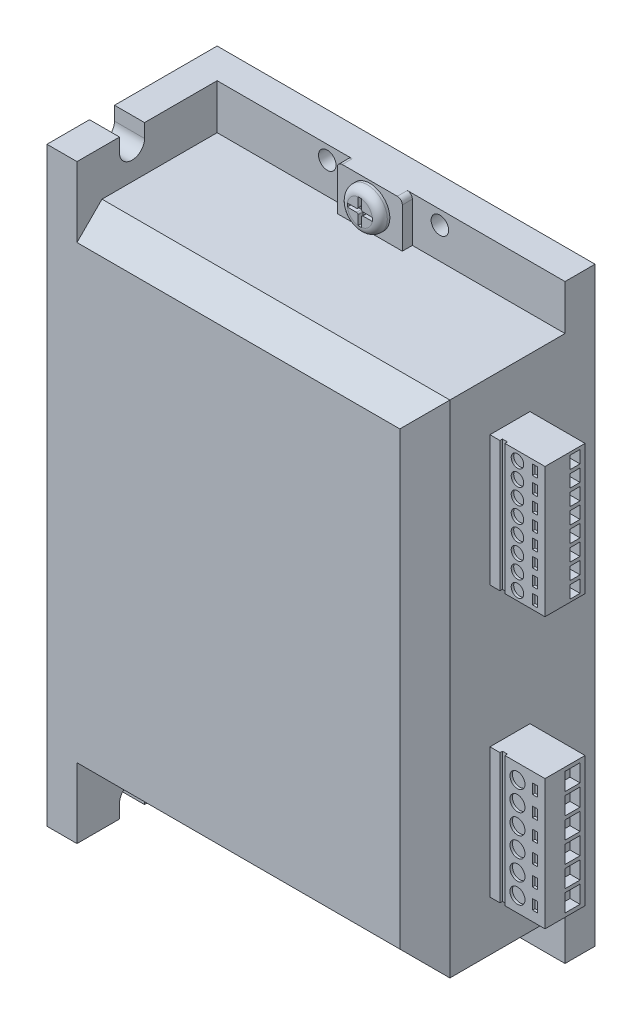
SolidWorks part; units mm, degrees
ref_plane "Front Plane" through (0, 0, 0) normal (0, 0, 1) x (1, 0, 0)
ref_plane "Top Plane" through (0, 0, 0) normal (0, 1, 0) x (1, 0, 0)
ref_plane "Right Plane" through (0, 0, 0) normal (1, 0, 0) x (0, 0, -1)
ref_axis "Axis_X" through (-88.99, 0, 0) along (1, 0, 0)
ref_axis "Axis_Y" through (0, 55, 0) along (0, -1, 0)
ref_axis "Axis_Z" through (0, 0, -88.99) along (0, 0, 1)
sketch "Sketch1" plane through (0, 0, 0) normal (0, 0, 1) x (1, 0, 0)
  line L0 (0, 0) -> (75.5, 0) construction
  line L1 (0, 59) -> (75.5, 59)
  line L2 (0, 59) -> (0, -59)
  line L3 (0, -59) -> (75.5, -59)
  line L4 (75.5, 59) -> (75.5, -59)
  dimension "FIX_101" = 118
  dimension "FIX_102" = 75.5
extrude "Boss-Extrude1" add sketch "Sketch1" along normal blind 34
sketch "Sketch2" plane through (0, 0, 34) normal (0, 0, 1) x (1, 0, 0)
  line L0 (0, 0) -> (75.5, 0) construction
  line L1 (0, 59) -> (0, -59) construction
  line L2 (75.5, -59) -> (75.5, 59) construction
  line L3 (75.5, 59) -> (0, 59) construction
  line L4 (6, 59) -> (75.5, 59)
  line L5 (6, 59) -> (6, 50)
  line L6 (6, 50) -> (75.5, 50)
  line L7 (75.5, 59) -> (75.5, 50)
  line L9 (75.5, -59) -> (6, -59)
  line L10 (75.5, -59) -> (75.5, -50)
  line L11 (75.5, -50) -> (6, -50)
  line L12 (6, -59) -> (6, -50)
  dimension "FIX_104" = 6
  dimension "FIX_105" = 9
extrude "Cut-Extrude1" cut sketch "Sketch2" against normal offset from surface (28 mm away) 6 up to face at (37.75, 0, 0)
sketch "Sketch3" plane through (0, 0, 6) normal (0, 0, 1) x (1, 0, 0)
  line L0 (75.5, 59) -> (6, 59) construction
  line L1 (33, 59) -> (44, 59)
  line L2 (32, 58) -> (32, 50)
  line L3 (32, 50) -> (45, 50)
  line L4 (45, 58) -> (45, 50)
  line L5 (6, 50) -> (75.5, 50) construction
  line L6 (75.5, -50) -> (6, -50) construction
  line L7 (32, -50) -> (45, -50)
  line L8 (32, -50) -> (32, -58)
  line L9 (33, -59) -> (44, -59)
  line L10 (45, -50) -> (45, -58)
  line L11 (6, -59) -> (75.5, -59) construction
  arc A0 (44, -59) -> (45, -58) centre (44, -58) ccw
  arc A1 (33, -59) -> (32, -58) centre (33, -58) cw
  arc A2 (44, 59) -> (45, 58) centre (44, 58) cw
  arc A3 (32, 58) -> (33, 59) centre (33, 58) cw
  point P19 (45, -59)
  point P26 (32, 59)
  dimension "FIX_109" = 1
  dimension "FIX_107" = 13
  dimension "FIX_108" = 32
extrude "Boss-Extrude2" add sketch "Sketch3" along normal blind 2
hole_wizard "DiameterHole1" positions "Sketch4" profile "Sketch5" hole size "Ø3.5" standard "JIS" end condition through all
sketch "Sketch4" plane through (0, 0, 6) normal (0, 0, 1) x (1, 0, 0)
  line L2 (75.5, -50) -> (75.5, 50) construction
  line L3 (0, 0) -> (50.5, 0) construction
  line L4 (0, 59) -> (0, -59) construction
  point P0 (28, 56.25)
  point P2 (50.5, 56.25)
  point P4 (50.5, -56.25)
  point P6 (28, -56.25)
  dimension "FIX_112" = 25
  dimension "FIX_113" = 22.5
  dimension "FIX_114" = 112.5
sketch "Sketch5" plane through (28, 56.25, 6) normal (1, 0, 0) x (0, -1, 0)
  line L0 (0, 0) -> (0, 6)
  line L1 (0, 6) -> (1.75, 6)
  line L2 (1.75, 6) -> (1.75, 0)
  line L5 (1.75, 0) -> (0, 0)
  line L11 (0, 0) -> (0, 6) construction
  dimension "FIX_111" = 3.5
  dimension "Thru Hole Depth" = 6
sketch "Sketch6" plane through (6, 0, 0) normal (1, 0, 0) x (0, 0, -1)
  line L0 (0, 0) -> (-34, 0) construction
  line L1 (0, -59) -> (0, 59) construction
  line L2 (-34, -50) -> (-34, 50) construction
  line L3 (-23, 56.25) -> (-23, 59) construction
  line L4 (-25.5, 56.25) -> (-25.5, 59)
  line L5 (-20.5, 56.25) -> (-20.5, 59)
  line L6 (-23, -56.25) -> (-23, -59) construction
  line L7 (-20.5, -56.25) -> (-20.5, -59)
  line L8 (-25.5, -56.25) -> (-25.5, -59)
  line L9 (-6, -59) -> (-34, -59) construction
  line L10 (-6, 59) -> (-34, 59) construction
  arc A0 (-25.5, 56.25) -> (-20.5, 56.25) centre (-23, 56.25) ccw
  arc A1 (-20.5, 59) -> (-25.5, 59) centre (-23, 59) ccw
  arc A2 (-20.5, -56.25) -> (-25.5, -56.25) centre (-23, -56.25) ccw
  arc A3 (-25.5, -59) -> (-20.5, -59) centre (-23, -59) ccw
  point P8 (-23, 57.625)
  point P13 (-23, -57.625)
  dimension "FIX_115" = 5
  dimension "FIX_116" = 112.5
  dimension "FIX_117" = 23
extrude "Cut-Extrude2" cut sketch "Sketch6" against normal through all
sketch "Sketch7" plane through (0, 0, 8) normal (0, 0, 1) x (1, 0, 0)
  line L0 (38.5, 59) -> (38.5, 50) construction
  line L3 (44, 59) -> (33, 59) construction
  line L4 (32, 50) -> (45, 50) construction
  line L5 (38.5, -50) -> (38.5, -59) construction
  line L6 (45, -50) -> (32, -50) construction
  line L7 (33, -59) -> (44, -59) construction
  circle A0 centre (38.5, 54.5) radius 4
  circle A1 centre (38.5, -54.5) radius 4
  point P8 (38.5, 54.5)
  dimension "FIX_118" = 8
extrude "Boss-Extrude3" add sketch "Sketch7" along normal blind 2 contours A0 | A1
fillet "Fillet1" radius 1.5 2 edges at (42.5, -54.5, 10) (42.5, 54.5, 10)
sketch "Sketch8" plane through (0, 0, 10) normal (0, 0, 1) x (1, 0, 0)
  line L0 (0, 0) -> (75.5, 0) construction
  line L1 (36, 54.85) -> (37.85, 54.85)
  line L2 (36, 54.85) -> (36, 54.15)
  line L3 (36, 54.15) -> (37.85, 54.15)
  line L4 (41, 54.85) -> (41, 54.15)
  line L5 (36, 54.85) -> (41, 54.15) construction
  line L6 (36, 54.15) -> (41, 54.85) construction
  line L7 (38.15, 57) -> (38.85, 57)
  line L8 (38.15, 57) -> (38.15, 55.15)
  line L9 (38.15, 52) -> (38.85, 52)
  line L10 (38.85, 57) -> (38.85, 55.15)
  line L11 (38.15, 57) -> (38.85, 52) construction
  line L12 (38.15, 52) -> (38.85, 57) construction
  line L13 (38.15, 53.85) -> (38.15, 52)
  line L14 (39.15, 54.15) -> (41, 54.15)
  line L15 (38.85, 53.85) -> (38.85, 52)
  line L16 (39.15, 54.85) -> (41, 54.85)
  line L17 (0, 59) -> (0, -59) construction
  line L18 (75.5, -50) -> (75.5, 50) construction
  line L19 (38.15, -52) -> (38.85, -57) construction
  line L20 (38.15, -57) -> (38.85, -52) construction
  line L21 (36, -54.15) -> (41, -54.85) construction
  line L22 (36, -54.85) -> (41, -54.15) construction
  line L23 (39.15, -54.85) -> (41, -54.85)
  line L24 (38.85, -53.85) -> (38.85, -52)
  line L25 (39.15, -54.15) -> (41, -54.15)
  line L26 (38.15, -53.85) -> (38.15, -52)
  line L27 (38.85, -57) -> (38.85, -55.15)
  line L28 (38.15, -52) -> (38.85, -52)
  line L29 (38.15, -57) -> (38.15, -55.15)
  line L30 (38.15, -57) -> (38.85, -57)
  line L31 (41, -54.85) -> (41, -54.15)
  line L32 (36, -54.15) -> (37.85, -54.15)
  line L33 (36, -54.85) -> (36, -54.15)
  line L34 (36, -54.85) -> (37.85, -54.85)
  arc A0 (37.85, 54.15) -> (38.15, 53.85) centre (37.85, 53.85) cw
  circle A1 centre (38.5, 54.5) radius 4 construction
  arc A2 (38.85, 53.85) -> (39.15, 54.15) centre (39.15, 53.85) cw
  arc A3 (39.15, 54.85) -> (38.85, 55.15) centre (39.15, 55.15) cw
  arc A4 (38.15, 55.15) -> (37.85, 54.85) centre (37.85, 55.15) cw
  arc A5 (38.15, -55.15) -> (37.85, -54.85) centre (37.85, -55.15) ccw
  arc A6 (39.15, -54.85) -> (38.85, -55.15) centre (39.15, -55.15) ccw
  arc A7 (38.85, -53.85) -> (39.15, -54.15) centre (39.15, -53.85) ccw
  arc A8 (37.85, -54.15) -> (38.15, -53.85) centre (37.85, -53.85) ccw
  point P6 (38.5, 54.5)
  point P36 (38.15, 54.15)
  point P39 (38.85, 54.15)
  point P42 (38.85, 54.85)
  point P45 (38.15, 54.85)
  point P53 (38.15, -54.85)
  point P54 (38.85, -54.85)
  point P55 (38.85, -54.15)
  point P56 (38.15, -54.15)
  point P57 (38.5, -54.5)
  dimension "FIX_123" = 0.3
  dimension "FIX_121" = 0.7
  dimension "FIX_122" = 5
extrude "Cut-Extrude3" cut sketch "Sketch8" against normal blind 1
sketch "Sketch9" plane through (75.5, 0, 0) normal (1, 0, 0) x (0, 0, -1)
  line L0 (0, 0) -> (-34, 0) construction
  line L1 (-21, 40) -> (-13, 40)
  line L2 (-21, 40) -> (-21, 14)
  line L3 (-21, 14) -> (-13, 14)
  line L4 (-13, 40) -> (-13, 14)
  line L5 (0, -59) -> (0, 59) construction
  line L6 (-34, -50) -> (-34, 50) construction
  line L7 (-17, 40) -> (-17, 0) construction
  line L8 (-13, -40) -> (-13, -14)
  line L9 (-21, -14) -> (-13, -14)
  line L10 (-21, -40) -> (-21, -14)
  line L11 (-21, -40) -> (-13, -40)
  dimension "FIX_125" = 8
  dimension "FIX_126" = 26
  dimension "FIX_127" = 28
extrude "Boss-Extrude4" add sketch "Sketch9" along normal blind 11
sketch "Sketch10" plane through (86.5, 0, 0) normal (1, 0, 0) x (0, 0, -1)
  line L0 (-14, 36.95) -> (-14, 36.25) construction
  line L1 (-16, 39.45) -> (-14, 39.45)
  line L2 (-16, 39.45) -> (-16, 36.95)
  line L3 (-16, 36.95) -> (-14, 36.95)
  line L4 (-14, 39.45) -> (-14, 36.95)
  line L5 (-16, 36.25) -> (-14, 36.25)
  line L6 (-16, 36.25) -> (-16, 33.75)
  line L7 (-16, 33.75) -> (-14, 33.75)
  line L8 (-14, 36.25) -> (-14, 33.75)
  line L9 (-16, 33.05) -> (-14, 33.05)
  line L10 (-16, 33.05) -> (-16, 30.55)
  line L11 (-16, 30.55) -> (-14, 30.55)
  line L12 (-14, 33.05) -> (-14, 30.55)
  line L13 (-16, 29.85) -> (-14, 29.85)
  line L14 (-16, 29.85) -> (-16, 27.35)
  line L15 (-16, 27.35) -> (-14, 27.35)
  line L16 (-14, 29.85) -> (-14, 27.35)
  line L17 (-16, 26.65) -> (-14, 26.65)
  line L18 (-16, 26.65) -> (-16, 24.15)
  line L19 (-16, 24.15) -> (-14, 24.15)
  line L20 (-14, 26.65) -> (-14, 24.15)
  line L21 (-16, 23.45) -> (-14, 23.45)
  line L22 (-16, 23.45) -> (-16, 20.95)
  line L23 (-16, 20.95) -> (-14, 20.95)
  line L24 (-14, 23.45) -> (-14, 20.95)
  line L25 (-14, 33.75) -> (-14, 33.05) construction
  line L26 (-14, 30.55) -> (-14, 29.85) construction
  line L27 (-14, 27.35) -> (-14, 26.65) construction
  line L28 (-14, 24.15) -> (-14, 23.45) construction
  line L29 (-13, 40) -> (-21, 40) construction
  line L30 (-14, 20.95) -> (-14, 20.25) construction
  line L31 (-13, 14) -> (-13, 40) construction
  line L32 (-16, 20.25) -> (-14, 20.25)
  line L33 (-13, -14) -> (-21, -14) construction
  line L34 (-14, -14.75) -> (-17, -14.75)
  line L35 (-16, 20.25) -> (-16, 17.75)
  line L36 (-16, 17.75) -> (-14, 17.75)
  line L37 (-14, 20.25) -> (-14, 17.75)
  line L38 (-16, 17.05) -> (-14, 17.05)
  line L39 (-16, 17.05) -> (-16, 14.55)
  line L40 (-16, 14.55) -> (-14, 14.55)
  line L41 (-14, 17.05) -> (-14, 14.55)
  line L42 (-14, 17.75) -> (-14, 17.05) construction
  line L43 (-14, -14.75) -> (-14, -18.25)
  line L44 (-14, -18.25) -> (-17, -18.25)
  line L48 (-17, -14.75) -> (-17, -18.25)
  line L49 (-14, -18.25) -> (-14, -18.95) construction
  line L50 (-17, -18.95) -> (-14, -18.95)
  line L51 (-17, -18.95) -> (-17, -22.45)
  line L52 (-17, -22.45) -> (-14, -22.45)
  line L53 (-14, -18.95) -> (-14, -22.45)
  line L54 (-17, -23.15) -> (-14, -23.15)
  line L55 (-17, -23.15) -> (-17, -26.65)
  line L56 (-17, -26.65) -> (-14, -26.65)
  line L57 (-14, -23.15) -> (-14, -26.65)
  line L58 (-17, -27.35) -> (-14, -27.35)
  line L59 (-17, -27.35) -> (-17, -30.85)
  line L60 (-17, -30.85) -> (-14, -30.85)
  line L61 (-14, -27.35) -> (-14, -30.85)
  line L62 (-17, -31.55) -> (-14, -31.55)
  line L63 (-17, -31.55) -> (-17, -35.05)
  line L64 (-17, -35.05) -> (-14, -35.05)
  line L65 (-14, -31.55) -> (-14, -35.05)
  line L66 (-17, -35.75) -> (-14, -35.75)
  line L67 (-17, -35.75) -> (-17, -39.25)
  line L68 (-17, -39.25) -> (-14, -39.25)
  line L69 (-14, -35.75) -> (-14, -39.25)
  line L70 (-14, -22.45) -> (-14, -23.15) construction
  line L71 (-14, -26.65) -> (-14, -27.35) construction
  line L72 (-14, -30.85) -> (-14, -31.55) construction
  line L73 (-14, -35.05) -> (-14, -35.75) construction
  line L74 (-13, -40) -> (-13, -14) construction
  dimension "FIX_129" = 2
  dimension "FIX_130" = 2.5
  dimension "FIX_131" = 0.7
  dimension "FIX_132" = 0.55
  dimension "FIX_133" = 1
  dimension "FIX_134" = 0.75
  dimension "FIX_135" = 0.7
  dimension "FIX_136" = 3.5
  dimension "FIX_137" = 3
  dimension "FIX_138" = 1
extrude "Cut-Extrude4" cut sketch "Sketch10" against normal blind 2
sketch "Sketch11" plane through (0, 0, 21) normal (0, 0, 1) x (1, 0, 0)
  line L0 (81, 40) -> (81, 14) construction
  line L1 (75.5, 40) -> (75.5, 14) construction
  line L2 (84, 36) -> (85, 36)
  line L3 (86.5, 40) -> (75.5, 40) construction
  line L4 (86.5, 14) -> (75.5, 14) construction
  line L5 (84, 36) -> (84, 34)
  line L6 (84, 39.2) -> (85, 39.2)
  line L7 (84, 39.2) -> (84, 37.2)
  line L8 (84, 37.2) -> (85, 37.2)
  line L9 (85, 39.2) -> (85, 37.2)
  line L10 (84, 39.2) -> (85, 37.2) construction
  line L11 (84, 37.2) -> (85, 39.2) construction
  line L12 (84, 34) -> (85, 34)
  line L13 (85, 36) -> (85, 34)
  line L14 (84, 36) -> (85, 34) construction
  line L15 (84, 34) -> (85, 36) construction
  line L16 (84, 32.8) -> (85, 32.8)
  line L17 (84, 32.8) -> (84, 30.8)
  line L18 (84, 30.8) -> (85, 30.8)
  line L19 (85, 32.8) -> (85, 30.8)
  line L20 (84, 32.8) -> (85, 30.8) construction
  line L21 (84, 30.8) -> (85, 32.8) construction
  line L22 (84, 29.6) -> (85, 29.6)
  line L23 (84, 29.6) -> (84, 27.6)
  line L24 (84, 27.6) -> (85, 27.6)
  line L25 (85, 29.6) -> (85, 27.6)
  line L26 (84, 29.6) -> (85, 27.6) construction
  line L27 (84, 27.6) -> (85, 29.6) construction
  line L28 (84, 26.4) -> (85, 26.4)
  line L29 (84, 26.4) -> (84, 24.4)
  line L30 (84, 24.4) -> (85, 24.4)
  line L31 (85, 26.4) -> (85, 24.4)
  line L32 (84, 26.4) -> (85, 24.4) construction
  line L33 (84, 24.4) -> (85, 26.4) construction
  line L34 (84, 23.2) -> (85, 23.2)
  line L35 (84, 23.2) -> (84, 21.2)
  line L36 (84, 21.2) -> (85, 21.2)
  line L37 (85, 23.2) -> (85, 21.2)
  line L38 (84, 23.2) -> (85, 21.2) construction
  line L39 (84, 21.2) -> (85, 23.2) construction
  line L40 (77.5, 40) -> (78.5, 40)
  line L41 (77.5, 40) -> (77.5, 14)
  line L42 (77.5, 14) -> (78.5, 14)
  line L43 (78.5, 40) -> (78.5, 14)
  line L44 (86.5, -14) -> (75.5, -14) construction
  line L45 (86.5, -40) -> (75.5, -40) construction
  line L46 (77.5, -14) -> (78.5, -14)
  line L47 (84, 20) -> (85, 20)
  line L48 (84, 20) -> (84, 18)
  line L49 (84, 18) -> (85, 18)
  line L50 (85, 20) -> (85, 18)
  line L51 (84, 20) -> (85, 18) construction
  line L52 (84, 18) -> (85, 20) construction
  line L53 (84, 16.8) -> (85, 16.8)
  line L54 (84, 16.8) -> (84, 14.8)
  line L55 (84, 14.8) -> (85, 14.8)
  line L56 (85, 16.8) -> (85, 14.8)
  line L57 (84, 16.8) -> (85, 14.8) construction
  line L58 (84, 14.8) -> (85, 16.8) construction
  line L59 (84, -16) -> (85, -16)
  line L60 (84, -16) -> (84, -18)
  line L61 (84, -18) -> (85, -18)
  line L62 (85, -16) -> (85, -18)
  line L63 (84, -16) -> (85, -18) construction
  line L64 (84, -18) -> (85, -16) construction
  line L65 (84, -20) -> (85, -20)
  line L66 (84, -20) -> (84, -22)
  line L67 (84, -22) -> (85, -22)
  line L68 (85, -20) -> (85, -22)
  line L69 (84, -20) -> (85, -22) construction
  line L70 (84, -22) -> (85, -20) construction
  line L71 (84, -24) -> (85, -24)
  line L72 (84, -24) -> (84, -26)
  line L73 (84, -26) -> (85, -26)
  line L74 (85, -24) -> (85, -26)
  line L75 (84, -24) -> (85, -26) construction
  line L76 (84, -26) -> (85, -24) construction
  line L77 (84, -28) -> (85, -28)
  line L78 (84, -28) -> (84, -30)
  line L79 (84, -30) -> (85, -30)
  line L80 (85, -28) -> (85, -30)
  line L81 (84, -28) -> (85, -30) construction
  line L82 (84, -30) -> (85, -28) construction
  line L83 (84, -32) -> (85, -32)
  line L84 (84, -32) -> (84, -34)
  line L85 (84, -34) -> (85, -34)
  line L86 (85, -32) -> (85, -34)
  line L87 (84, -32) -> (85, -34) construction
  line L88 (84, -34) -> (85, -32) construction
  line L89 (84, -36) -> (85, -36)
  line L90 (84, -36) -> (84, -38)
  line L91 (84, -38) -> (85, -38)
  line L92 (85, -36) -> (85, -38)
  line L93 (84, -36) -> (85, -38) construction
  line L94 (84, -38) -> (85, -36) construction
  line L95 (84.5, -17) -> (84.5, -21) construction
  line L96 (84.5, -21) -> (84.5, -25) construction
  line L97 (84.5, -25) -> (84.5, -29) construction
  line L98 (84.5, -29) -> (84.5, -33) construction
  line L99 (84.5, -33) -> (84.5, -37) construction
  line L100 (84.5, 15.8) -> (84.5, 19) construction
  line L101 (84.5, 19) -> (84.5, 22.2) construction
  line L102 (84.5, 22.2) -> (84.5, 25.4) construction
  line L103 (84.5, 25.4) -> (84.5, 28.6) construction
  line L104 (84.5, 28.6) -> (84.5, 31.8) construction
  line L105 (84.5, 31.8) -> (84.5, 35) construction
  line L106 (84.5, 35) -> (84.5, 38.2) construction
  line L107 (77.5, -14) -> (77.5, -40)
  line L108 (77.5, -40) -> (78.5, -40)
  line L109 (78.5, -14) -> (78.5, -40)
  line L110 (81, -14) -> (81, -40) construction
  line L111 (86.5, -14) -> (86.5, -40) construction
  circle A0 centre (81, 38.2) radius 1.25
  circle A1 centre (81, 35) radius 1.25
  circle A2 centre (81, 31.8) radius 1.25
  circle A3 centre (81, 28.6) radius 1.25
  circle A4 centre (81, 25.4) radius 1.25
  circle A5 centre (81, 22.2) radius 1.25
  circle A6 centre (81, 19) radius 1.25
  circle A7 centre (81, 15.8) radius 1.25
  circle A8 centre (81, -17) radius 1.5
  circle A9 centre (81, -21) radius 1.5
  circle A10 centre (81, -25) radius 1.5
  circle A11 centre (81, -29) radius 1.5
  circle A12 centre (81, -33) radius 1.5
  circle A13 centre (81, -37) radius 1.5
  point P18 (84.5, 38.2)
  point P23 (84.5, 35)
  point P28 (84.5, 31.8)
  point P33 (84.5, 28.6)
  point P38 (84.5, 25.4)
  point P43 (84.5, 22.2)
  point P54 (84.5, 19)
  point P59 (84.5, 15.8)
  point P68 (84.5, -17)
  point P73 (84.5, -21)
  point P78 (84.5, -25)
  point P83 (84.5, -29)
  point P88 (84.5, -33)
  point P93 (84.5, -37)
  dimension "FIX_140" = 2.5
  dimension "FIX_152" = 3
  dimension "FIX_141" = 1.8
  dimension "FIX_142" = 3.2
  dimension "FIX_143" = 2
  dimension "FIX_144" = 1
  dimension "FIX_145" = 3.5
  dimension "FIX_146" = 1
  dimension "FIX_147" = 2
  dimension "FIX_148" = 3
  dimension "FIX_149" = 4
  dimension "FIX_150" = 1
  dimension "FIX_151" = 2
extrude "Cut-Extrude5" cut sketch "Sketch11" against normal blind 0.5
chamfer "Chamfer1" distance 5 angle 45 3 edges at (40.75, -50, 34) (75.5, 0, 34) (40.75, 50, 34)
equation "\"Factor\"= 1.082532"
